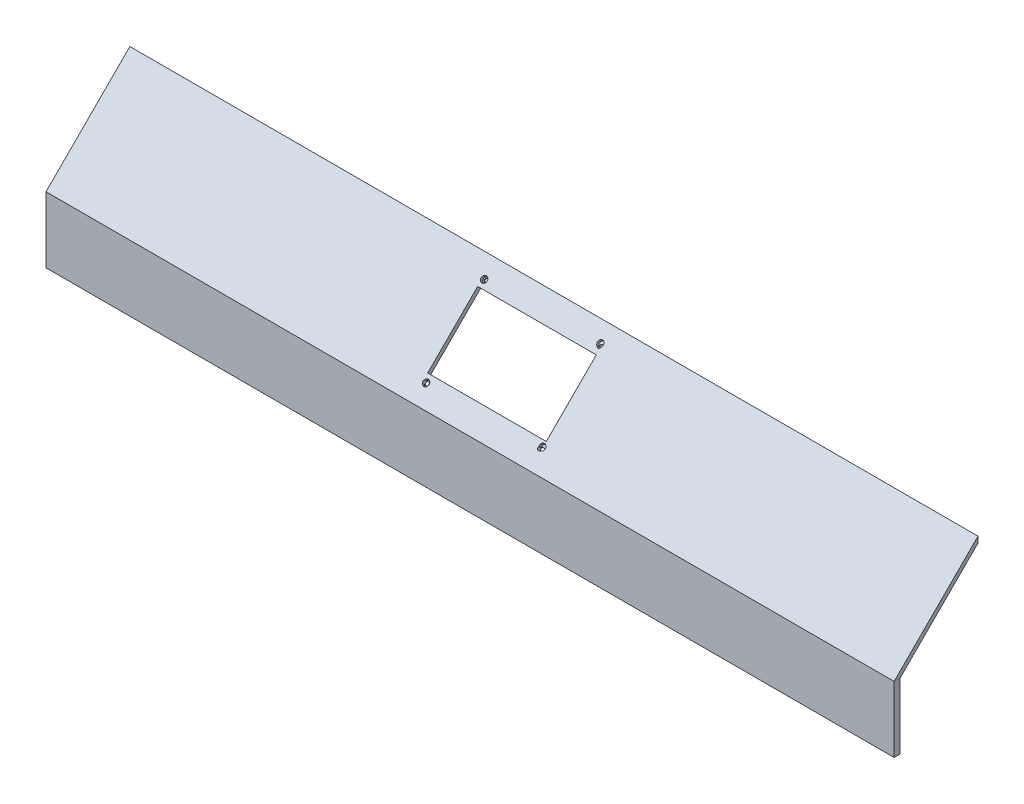
SolidWorks part; units mm, degrees
ref_plane "Front Plane" through (0, 0, 0) normal (0, 0, 1) x (1, 0, 0)
ref_plane "Top Plane" through (0, 0, 0) normal (0, 1, 0) x (1, 0, 0)
ref_plane "Right Plane" through (0, 0, 0) normal (1, 0, 0) x (0, 0, -1)
sketch "Sketch1" plane through (0, 0, 0) normal (1, 0, 0) x (0, 0, -1)
  line L0 (0, 0) -> (0, 55)
  line L1 (0, 55) -> (70, 125)
  line L2 (70, 125) -> (70, 120)
  line L3 (70, 120) -> (5, 55)
  line L4 (5, 55) -> (5, 0)
  line L5 (5, 0) -> (0, 0)
  dimension "D1" = 55
  dimension "D2" = 55
  dimension "D3" = 135
  dimension "D4" = 65
  dimension "D5" = 5
extrude "Boss-Extrude1" add sketch "Sketch1" along normal blind 708
sketch "Sketch2" plane through (0, 27.5, 27.5) normal (0, 0.7071, 0.7071) x (1, 0, 0)
  line L1 (301, 48.3883) -> (407, 48.3883)
  line L2 (301, 48.3883) -> (301, 128.3883)
  line L3 (301, 128.3883) -> (407, 128.3883)
  line L4 (407, 48.3883) -> (407, 128.3883)
  line L6 (708, 137.8858) -> (0, 137.8858) construction
  line L7 (708, 38.8909) -> (0, 38.8909) construction
  line L8 (354, 38.8909) -> (354, 137.8858)
  line L9 (708, 137.8858) -> (708, 38.8909) construction
  line L10 (306, 123.3883) -> (402, 123.3883)
  line L11 (402, 123.3883) -> (402, 53.3883)
  line L12 (402, 53.3883) -> (306, 53.3883)
  line L13 (306, 53.3883) -> (306, 123.3883)
  line L15 (304.5, 117.8883) -> (403.5, 117.8883)
  line L16 (304.5, 117.8883) -> (304.5, 58.8883)
  line L17 (304.5, 58.8883) -> (403.5, 58.8883)
  line L18 (403.5, 117.8883) -> (403.5, 58.8883)
  circle A0 centre (306, 123.3883) radius 1.6
  circle A1 centre (402, 123.3883) radius 1.6
  circle A2 centre (402, 53.3883) radius 1.6
  circle A3 centre (306, 53.3883) radius 1.6
  point P6 (407, 88.3883)
  point P13 (354, 88.3883)
  point P14 (354, 128.3883)
  point P27 (354, 117.8883)
  point P28 (403.5, 88.3883)
  dimension "D6" = 3.2
  dimension "D1" = 80
  dimension "D2" = 106
  dimension "D3" = 354
  dimension "D4" = 0
  dimension "D5" = 0
  dimension "D7" = 70
  dimension "D8" = 96
  dimension "D9" = 5
  dimension "D10" = 5
  dimension "D11" = 59
  dimension "D12" = 99
  dimension "D13" = 0
  dimension "D14" = 0
extrude "Cut-Extrude1" cut sketch "Sketch2" against normal blind 708 contours A0 | A1 | A2 | A3 | L16 L15 L18 L17
sketch "Sketch3" plane through (0, 0, -5) normal (0, 0, -1) x (-1, 0, 0)
  line L0 (-708, 0) -> (-708, 55) construction
  line L1 (-684, 50) -> (-679, 50)
  line L2 (-684, 50) -> (-684, 40)
  line L3 (-684, 40) -> (-679, 40)
  line L4 (-679, 50) -> (-679, 40)
  line L5 (-684, 20) -> (-679, 20)
  line L6 (-684, 20) -> (-684, 10)
  line L7 (-684, 10) -> (-679, 10)
  line L8 (-679, 20) -> (-679, 10)
  line L9 (-708, 0) -> (0, 0) construction
  line L10 (-708, 55) -> (0, 55) construction
  dimension "D1" = 10
  dimension "D2" = 10
  dimension "D3" = 24
  dimension "D4" = 24
  dimension "D5" = 5
  dimension "D6" = 5
  dimension "D7" = 10
  dimension "D8" = 5
extrude "Boss-Extrude2" add sketch "Sketch3" along normal blind 20
fillet "Fillet1" radius 5 4 edges at (681.5, 10, -25) (681.5, 20, -25) (681.5, 40, -25) (681.5, 50, -25)
sketch "Sketch4" plane through (684, 0, 0) normal (1, 0, 0) x (0, 0, -1)
  line L0 (20, 50) -> (5, 50) construction
  line L1 (5, 50) -> (5, 40) construction
  line L2 (20, 20) -> (5, 20) construction
  line L3 (5, 20) -> (5, 10) construction
  circle A0 centre (15, 45) radius 2.65
  circle A1 centre (15, 15) radius 2.65
  dimension "D3" = 5.3
  dimension "D4" = 5.3
  dimension "D1" = 5
  dimension "D2" = 10
  dimension "D5" = 5
  dimension "D6" = 10
extrude "Cut-Extrude2" cut sketch "Sketch4" against normal blind 10
ref_plane "Plane1" through (354, 0, 0) normal (1, 0, 0) x (0, 0, -1)
sketch "Sketch6" plane through (0, 27.5, 27.5) normal (0, 0.7071, 0.7071) x (1, 0, 0)
  circle A0 centre (306, 123.3883) radius 2.5
  circle A1 centre (401.9888, 124.8526) radius 2.5
  circle A2 centre (403.0565, 54.8608) radius 2.5
  circle A3 centre (307.0677, 53.3965) radius 2.5
  dimension "D1" = 5
  dimension "D2" = 2
  dimension "D3" = 2
extrude "Cut-Extrude3" cut sketch "Sketch6" against normal blind 2.5
ref_plane "Plane2" through (0, 55, 0) normal (0, -1, 0) x (-1, 0, 0)
split "Split1" trim tools "Plane2" bodies to split 106 resulting bodies 109 110
